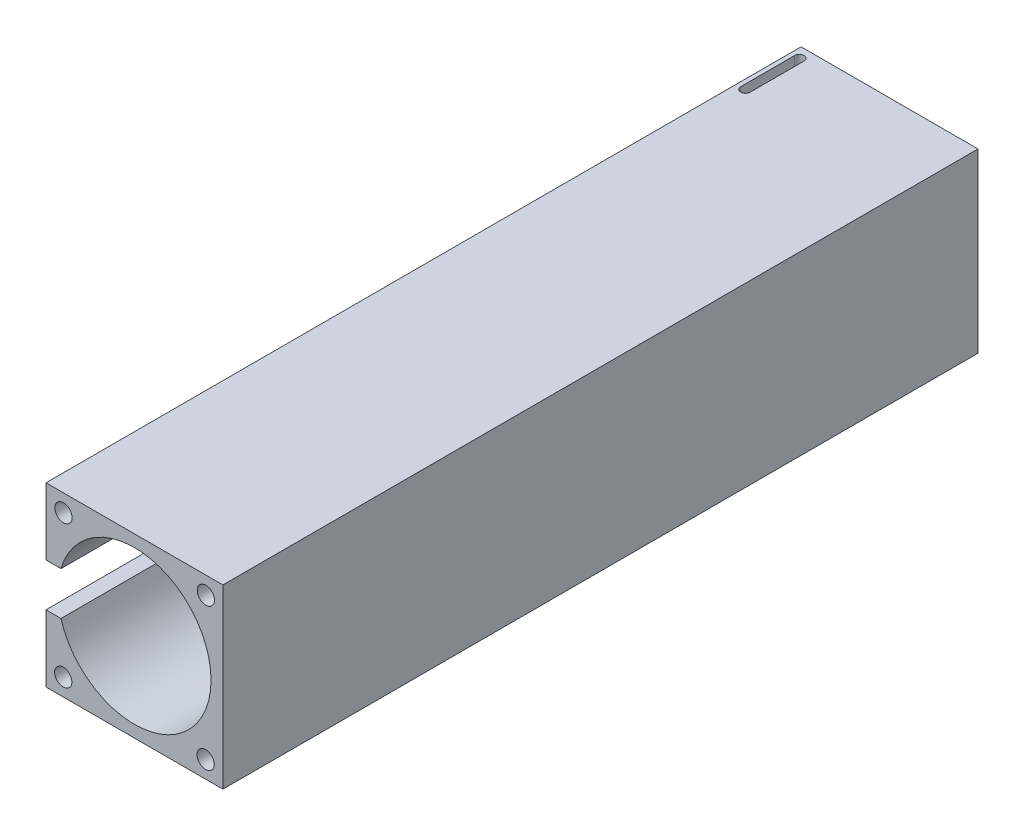
SolidWorks part; units mm, degrees
ref_plane "前基準面" through (0, 0, 0) normal (0, 0, 1) x (1, 0, 0)
ref_plane "上基準面" through (0, 0, 0) normal (0, 1, 0) x (1, 0, 0)
ref_plane "右基準面" through (0, 0, 0) normal (1, 0, 0) x (0, 0, -1)
ref_axis "基準軸1" through (0, -55, 0) along (0, 1, 0)
ref_axis "基準軸2" through (-88.99, 0, 0) along (1, 0, 0)
ref_axis "基準軸3" through (0, 0, 55) along (0, 0, -1)
sketch "草圖1" plane through (0, 0, 0) normal (0, 0, 1) x (1, 0, 0)
  line L0 (0, -55) -> (0, 55) construction
  line L1 (-41, -41) -> (41, -41)
  line L2 (-41, -41) -> (-41, 41)
  line L3 (-41, 41) -> (41, 41)
  line L4 (41, -41) -> (41, 41)
  line L5 (55, 0) -> (-55, 0) construction
  circle A0 centre (0, 0) radius 35.5
  point P7 (0, -41)
  point P10 (41, 0)
  dimension "D1" = 71
  dimension "D2" = 82
  dimension "D3" = 82
extrude "填料-伸長1" add sketch "草圖1" along normal blind 315
sketch "草圖2" plane through (0, 0, 0) normal (0, 0, -1) x (-1, 0, 0)
  line L1 (-41, 41) -> (41, 41)
  line L2 (-41, 41) -> (-41, -41)
  line L3 (-41, -41) -> (41, -41)
  line L4 (41, 41) -> (41, -41)
extrude "填料-伸長2" add sketch "草圖2" along normal blind 35
ref_plane "平面1" through (0, 0, -17.5) normal (0, 0, -1) x (-1, 0, 0)
sketch "草圖3" plane through (0, 0, 315) normal (0, 0, 1) x (1, 0, 0)
  line L0 (-41, 41) -> (-41, -41) construction
  line L1 (-41, 10) -> (-33, 10)
  line L2 (-41, 10) -> (-41, -10)
  line L3 (-41, -10) -> (-33, -10)
  line L4 (-33, 10) -> (-33, -10)
  line L6 (55, 0) -> (-55, 0) construction
  point P6 (-33, 0)
  dimension "D1" = 8
  dimension "D2" = 20
extrude "除料-伸長1" cut sketch "草圖3" against normal up to surface (315 mm away) up to face at (35.5, 0, 0)
sketch "草圖4" plane through (0, 0, 315) normal (0, 0, 1) x (1, 0, 0)
  line L1 (41, 41) -> (-41, 41) construction
  line L2 (-41, 41) -> (-41, 10) construction
  line L3 (-41, -41) -> (41, -41) construction
  line L4 (-41, -10) -> (-41, -41) construction
  circle A0 centre (-32.9, 33) radius 4
  circle A1 centre (33.1, 32.9) radius 4
  circle A2 centre (33, -33.1) radius 4
  circle A3 centre (-33, -33) radius 4
  point P15 (0.05, -0.05)
  dimension "D1" = 8
  dimension "D5" = 8
  dimension "D2" = 8
  dimension "D3" = 8.1
  dimension "D6" = 8
  dimension "D4" = 4
extrude "除料-伸長2" cut sketch "草圖4" against normal blind 20
fillet "圓角2" radius 3 1 edges at (-28.9, 33, 295)
fillet "圓角3" radius 3 1 edges at (37.1, 32.9, 295)
fillet "圓角4" radius 3 1 edges at (-29, -33, 295)
fillet "圓角5" radius 3 1 edges at (37, -33.1, 295)
sketch "草圖5" plane through (0, 41, 0) normal (0, 1, 0) x (1, 0, 0)
  line L0 (-36.8, 5) -> (-36.8, 30) construction
  line L1 (-39, 5) -> (-39, 30)
  line L2 (-34.6, 5) -> (-34.6, 30)
  line L3 (45.1, 17.5) -> (-45.1, 17.5) construction
  line L5 (-41, -315) -> (-41, 35) construction
  arc A0 (-39, 5) -> (-34.6, 5) centre (-36.8, 5) ccw
  arc A1 (-34.6, 30) -> (-39, 30) centre (-36.8, 30) ccw
  point P2 (-36.8, 17.5)
  dimension "D1" = 2.2
  dimension "D2" = 25
  dimension "D3" = 2
extrude "除料-伸長3" cut sketch "草圖5" against normal blind 12
sketch "草圖6" plane through (-41, 0, 0) normal (-1, 0, 0) x (0, 0, 1)
  line L1 (-32.2, 33) -> (-2.8, 33)
  line L2 (-32.2, 33) -> (-32.2, 36)
  line L3 (-32.2, 36) -> (-2.8, 36)
  line L4 (-2.8, 33) -> (-2.8, 36)
  line L5 (-17.5, 45.1) -> (-17.5, -45.1) construction
  line L6 (315, 41) -> (-35, 41) construction
  point P4 (-17.5, 36)
  dimension "D1" = 29.4
  dimension "D2" = 3
  dimension "D3" = 5
extrude "除料-伸長4" cut sketch "草圖6" against normal blind 10
